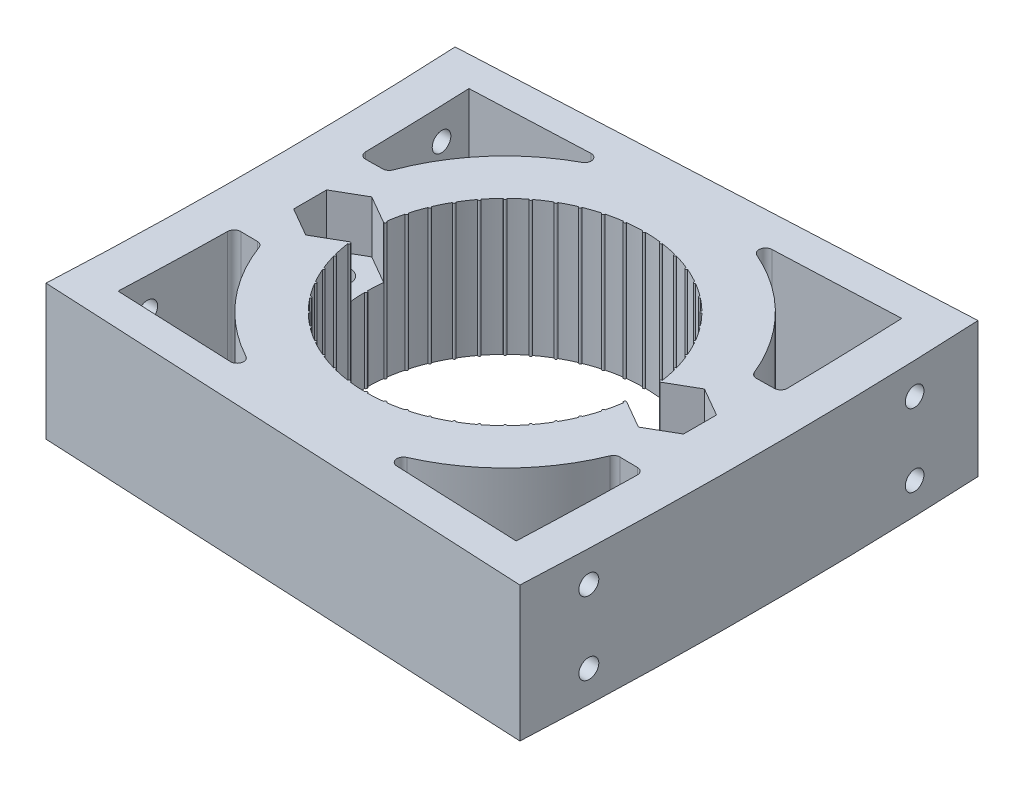
SolidWorks part; units mm, degrees
ref_plane "Front Plane" through (0, 0, 0) normal (0, 0, 1) x (1, 0, 0)
ref_plane "Top Plane" through (0, 0, 0) normal (0, 1, 0) x (1, 0, 0)
ref_plane "Right Plane" through (0, 0, 0) normal (1, 0, 0) x (0, 0, -1)
sketch "Sketch1" plane through (0, 0, 0) normal (0, 1, 0) x (1, 0, 0)
  line L0 (711.9611, 34.9764) -> (0, 0) construction
  line L1 (0, 0) -> (711.9611, -34.9764) construction
  line L2 (635.8529, 31.2375) -> (711.9611, 34.9764)
  line L3 (635.8529, -31.2375) -> (711.9611, -34.9764)
  circle A0 centre (0, 0) radius 636.6198 construction
  circle A1 centre (0, 0) radius 712.8198 construction
  arc A2 (711.9611, -34.9764) -> (711.9611, 34.9764) centre (0, 0) ccw
  arc A3 (635.8529, -31.2375) -> (635.8529, 31.2375) centre (0, 0) ccw
  dimension "D1" = 1273.2395
  dimension "D2" = 76.2
  dimension "D3" = 5.625
extrude "TrackTop" add sketch "Sketch1" along normal blind 20.6375
sketch "Sketch6" plane through (0, 0, 0) normal (0, 1, 0) x (1, 0, 0)
  line L0 (636.6198, 0) -> (0, 0) construction
  line L1 (636.6198, 0) -> (649.3198, 0) construction
  line L2 (649.3198, 0) -> (700.1198, 0) construction
  line L3 (700.1198, 0) -> (712.8198, 0) construction
  circle A0 centre (649.3198, 0) radius 1.8288
  circle A1 centre (700.1198, 0) radius 1.8288
  circle A4 centre (0, 0) radius 712.8198 construction
  circle A5 centre (0, 0) radius 636.6198 construction
  point P0 (0, 0)
  dimension "D1" = 3.6576
  dimension "D2" = 12.7
extrude "MountingHoles" cut sketch "Sketch6" along normal through all both and the other way through all
sketch "Sketch9" plane through (0, 0, 0) normal (0, 1, 0) x (1, 0, 0)
  line L0 (0, 0) -> (755.0104, 26.3655) construction
  line L1 (0, 0) -> (983.0347, 0) construction
  dimension "D1" = 2
sketch "Sketch7" plane through (0, 20.6375, 0) normal (0, 1, 0) x (1, 0, 0)
  line L0 (712.8198, 0) -> (636.6198, 0) construction
  arc A0 (711.9611, -34.9764) -> (711.9611, 34.9764) centre (0, 0) ccw construction
  arc A1 (635.8529, -31.2375) -> (635.8529, 31.2375) centre (0, 0) ccw construction
  circle A2 centre (674.7198, 0) radius 21.25
  dimension "D1" = 42.5
extrude "Cut-Extrude1" cut sketch "Sketch7" against normal through all
sketch "Sketch15" plane through (0, 0, 0) normal (0, 1, 0) x (1, 0, 0)
  line L0 (674.7198, 21.25) -> (674.7198, -21.25) construction
  circle A0 centre (674.7198, 0) radius 21.25 construction
  circle A1 centre (674.7198, 0) radius 21.25 construction
  circle A2 centre (674.7198, 21.25) radius 0.2
  point P2 (674.7198, 0)
  dimension "D1" = 0.4
sketch "Sketch16" plane through (0, 0, 0) normal (0, 0, 1) x (1, 0, 0)
  line L0 (674.7198, 0) -> (674.7198, 28.4843) construction
  point P2 (0, 0)
extrude "Boss-Extrude1" add sketch "Sketch15" along normal up to surface (20.6375 mm away) up to face at (674.7198, 20.6375, 21.25)
pattern_circular "CirPattern1" count 48 over 360 about axis through (674.7198, 0, 0) along (0, 1, 0) of "Boss-Extrude1" reverse direction yes
sketch "Sketch8" plane through (0, 20.6375, 0) normal (0, 1, 0) x (1, 0, 0)
  line L1 (653.6854, -2.5205) -> (653.6854, 2.5205)
  line L2 (653.6854, 2.5205) -> (649.3198, 5.041)
  line L3 (649.3198, 5.041) -> (644.9541, 2.5205)
  line L4 (644.9541, 2.5205) -> (644.9541, -2.5205)
  line L5 (644.9541, -2.5205) -> (649.3198, -5.041)
  line L6 (649.3198, -5.041) -> (653.6854, -2.5205)
  line L7 (704.4854, -2.5205) -> (704.4854, 2.5205)
  line L8 (704.4854, 2.5205) -> (700.1198, 5.041)
  line L9 (700.1198, 5.041) -> (695.7541, 2.5205)
  line L10 (695.7541, 2.5205) -> (695.7541, -2.5205)
  line L11 (695.7541, -2.5205) -> (700.1198, -5.041)
  line L12 (700.1198, -5.041) -> (704.4854, -2.5205)
  circle A0 centre (649.3198, 0) radius 4.3656 construction
  circle A1 centre (700.1198, 0) radius 4.3656 construction
  point P10 (644.9541, 0)
  dimension "D1" = 8.7312
extrude "Cut-Extrude2" cut sketch "Sketch8" against normal blind 7.9375
sketch "Sketch13" plane through (0, 20.6375, 0) normal (0, 1, 0) x (1, 0, 0)
  line L0 (642.4114, 26.7914) -> (705.8562, 29.4373) construction
  line L1 (642.4114, -26.7914) -> (705.8562, -29.4373) construction
  line L2 (642.4114, -26.7914) -> (0, 0) construction
  line L3 (642.4114, 26.7914) -> (0, 0) construction
  line L4 (-200000, 0) -> (200983.0347, 0) construction
  line L5 (635.8529, 31.2375) -> (711.9611, 34.9764) construction
  line L6 (642.8992, 9.525) -> (642.8992, -9.525) construction
  line L7 (706.3922, 10.4657) -> (701.9914, 10.4005)
  line L8 (642.8992, 9.525) -> (647.152, 9.588)
  line L9 (647.152, -9.588) -> (642.8992, -9.525)
  line L10 (706.3922, -10.4657) -> (701.9914, -10.4005)
  line L11 (642.8992, 9.525) -> (0, 0)
  line L12 (642.8992, -9.525) -> (0, 0)
  line L13 (665.7134, 27.7632) -> (642.4114, 26.7914)
  line L14 (705.8562, 29.4373) -> (681.3832, 28.4167)
  line L15 (705.8562, -29.4373) -> (681.3832, -28.4167)
  line L16 (665.7134, -27.7632) -> (642.4114, -26.7914)
  arc A0 (642.4114, -26.7914) -> (642.8992, -9.525) centre (0, 0) ccw
  arc A1 (705.8562, -29.4373) -> (706.3922, -10.4657) centre (0, 0) ccw
  arc A2 (642.8992, 9.525) -> (642.4114, 26.7914) centre (0, 0) ccw
  arc A3 (706.3922, 10.4657) -> (705.8562, 29.4373) centre (0, 0) ccw
  circle A4 centre (674.7198, 0) radius 29.1875 construction
  circle A5 centre (674.7198, 0) radius 21.25 construction
  arc A6 (635.8529, -31.2375) -> (635.8529, 31.2375) centre (0, 0) ccw construction
  arc A7 (711.9611, -34.9764) -> (711.9611, 34.9764) centre (0, 0) ccw construction
  arc A8 (647.152, 9.588) -> (665.7134, 27.7632) centre (674.7198, 0) cw
  arc A9 (701.9914, 10.4005) -> (681.3832, 28.4167) centre (674.7198, 0) ccw
  arc A10 (701.9914, -10.4005) -> (681.3832, -28.4167) centre (674.7198, 0) cw
  arc A11 (647.152, -9.588) -> (665.7134, -27.7632) centre (674.7198, 0) ccw
  point P18 (642.8992, 0)
  dimension "D2" = 6.35
  dimension "D3" = 6.35
  dimension "D5" = 7.9375
  dimension "D1" = 4.7625
  dimension "D4" = 19.05
extrude "Cut-Extrude5" cut sketch "Sketch13" against normal through all contours A11 L9 A0 L16 | L8 A8 L13 A2 | A9 L7 A3 L14 | L10 A10 L15 A1 region at (699.2431, 20.6375, -22.2451) region at (649.1861, 20.6375, -20.715) region at (649.1861, 20.6375, 20.715) region at (699.2431, 20.6375, 22.2451)
fillet "Fillet1" radius 1 12 edges at (647.152, 10.3187, 9.588) (642.8992, 10.3187, 9.525) (701.9914, 10.3187, 10.4005) (706.3922, 10.3187, 10.4657) (701.9914, 10.3187, -10.4005) (706.3922, 10.3187, -10.4657) (647.152, 10.3187, -9.588) (642.8992, 10.3187, -9.525) (665.7134, 10.3187, 27.7632) (681.3832, 10.3187, 28.4167) (665.7134, 10.3187, -27.7632) (681.3832, 10.3187, -28.4167)
ref_plane "Plane1" through (636.232, 0, -22.2177) normal (-0.9994, 0, 0.0349) x (0.0349, 0, 0.9994)
sketch "Sketch10" plane through (636.232, 0, -22.2177) normal (-0.9994, 0, 0.0349) x (0.0349, 0, 0.9994)
  line L0 (0, 0) -> (0, 20.6375) construction
  line L1 (59.8022, 20.6375) -> (-10.108, 20.6375) construction
  line L2 (0, 15.875) -> (0, 4.7625) construction
  circle A0 centre (0, 15.875) radius 1.4732
  circle A1 centre (0, 4.7625) radius 1.4732
  point P9 (0, 10.3187)
  dimension "D1" = 2.9464
  dimension "D2" = 4.7625
extrude "Cut-Extrude3" cut sketch "Sketch10" against normal up to next and the other way through all
ref_plane "Plane2" through (712.3855, 0, -24.8771) normal (0.9994, 0, -0.0349) x (-0.0349, 0, -0.9994)
sketch "Sketch14" plane through (712.3855, 0, -24.8771) normal (0.9994, 0, -0.0349) x (-0.0349, 0, -0.9994)
  circle A0 centre (0, 15.875) radius 1.4732 construction
  circle A1 centre (0, 15.875) radius 1.4732
  circle A2 centre (0, 4.7625) radius 1.4732 construction
  circle A3 centre (0, 4.7625) radius 1.4732
extrude "Cut-Extrude6" cut sketch "Sketch14" against normal up to next and the other way through all
mirror "Mirror1" about plane through (0, 0, 0) normal (0, 0, 1) of "Cut-Extrude6", "Cut-Extrude3"
equation "\"InternalCircumference\"= 4m"
equation "\"D1@Sketch1\"=\"InternalCircumference\"/PI"
equation "\"TrackWidth\"=76.2"
equation "\"D2@Sketch1\"=\"TrackWidth\""
equation "\"WallStudDiameter\"=6.35"
equation "\"SandwichBoltDiameter\"= 0.1440in'6-32"
equation "\"HoleEdgeSpacing\"= 1in / 2"
equation "\"D2@Sketch6\"=\"HoleEdgeSpacing\""
equation "\"TeeNutWidth\"= 6.35'4-40"
equation "\"TeeNutHeight\"= 2.38125'4-40"
equation "\"TeeNutDrillSize\"= 3.048'4-40"
equation "\"HollowWallThickness\"=9.525"
equation "\"LegHoleDiameter\" = 42.5mm'1.25 in PVC"
equation "\"D3@Sketch1\"=360/64"
equation "\"D1@Sketch7\"=\"LegHoleDiameter\""
equation "\"D1@Sketch8\"=(5in/16)*1.1"
